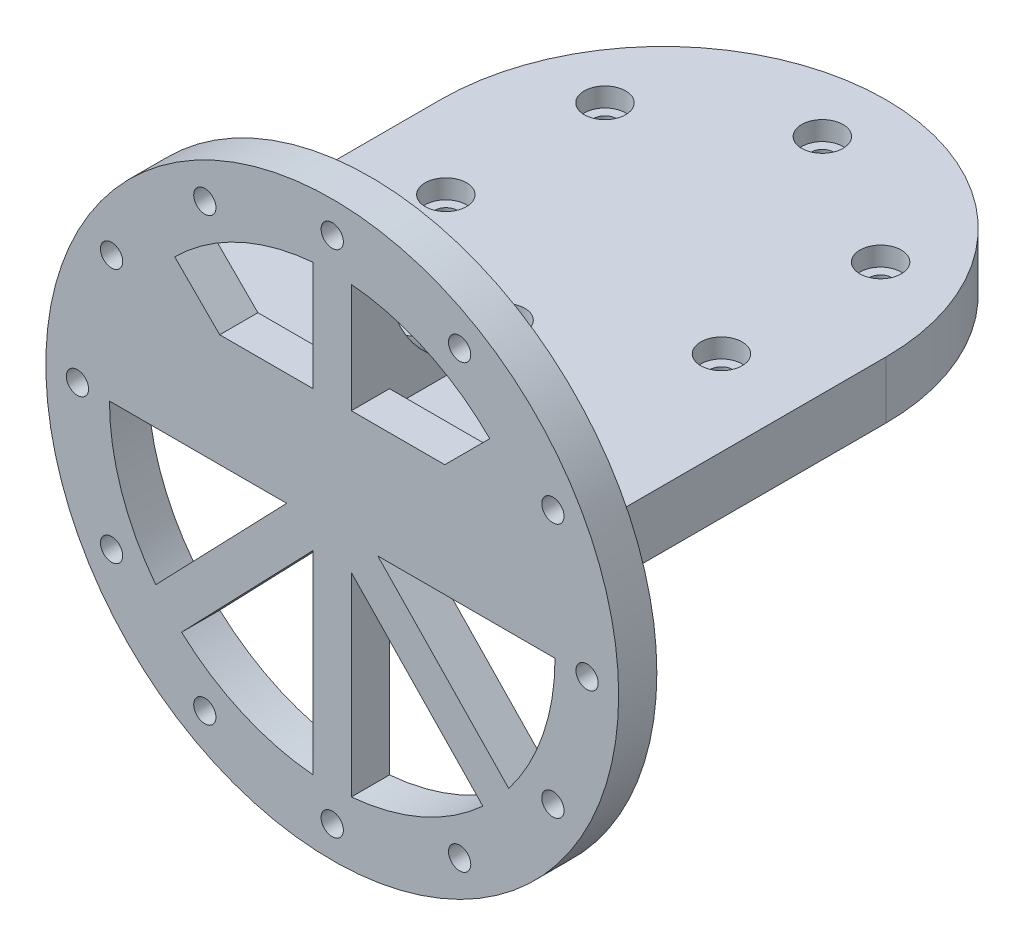
SolidWorks part; units mm, degrees
ref_plane "Front Plane" through (0, 0, 0) normal (0, 0, 1) x (1, 0, 0)
ref_plane "Top Plane" through (0, 0, 0) normal (0, 1, 0) x (1, 0, 0)
ref_plane "Right Plane" through (0, 0, 0) normal (1, 0, 0) x (0, 0, -1)
sketch "Sketch1" plane through (0, 0, 0) normal (0, 1, 0) x (1, 0, 0)
  circle A0 centre (0, 0) radius 35
  dimension "D1" = 70
extrude "Boss-Extrude1" add sketch "Sketch1" along normal blind 9
sketch "Sketch2" plane through (0, 0, 0) normal (0, -1, 0) x (1, 0, 0)
  circle A0 centre (0, 0) radius 30
  dimension "D1" = 60
extrude "Cut-Extrude1" cut sketch "Sketch2" against normal blind 3
sketch "Sketch3" plane through (0, 9, 0) normal (0, 1, 0) x (1, 0, 0)
  line L0 (0, 0) -> (0, -25) construction
  circle A0 centre (0, 0) radius 25 construction
  circle A1 centre (0, -25) radius 1.75
  circle A2 centre (-21.6506, -12.5) radius 1.75
  circle A3 centre (-21.6506, 12.5) radius 1.75
  circle A4 centre (0, 25) radius 1.75
  circle A5 centre (21.6506, 12.5) radius 1.75
  circle A6 centre (21.6506, -12.5) radius 1.75
  point P17 (0, 0)
  dimension "D1" = 50
  dimension "D2" = 3.5
  dimension "D3" = 6
extrude "Cut-Extrude2" cut sketch "Sketch3" against normal through all
sketch "Sketch4" plane through (0, 9, 0) normal (0, 1, 0) x (1, 0, 0)
  circle A0 centre (0, 25) radius 3.25
  circle A1 centre (21.6506, 12.5) radius 3.25
  circle A2 centre (21.6506, -12.5) radius 3.25
  circle A3 centre (0, -25) radius 3.25
  circle A4 centre (-21.6506, -12.5) radius 3.25
  circle A5 centre (-21.6506, 12.5) radius 3.25
  point P15 (0, 0)
  dimension "D1" = 6.5
  dimension "D2" = 6
extrude "Cut-Extrude3" cut sketch "Sketch4" against normal blind 3
sketch "Sketch5" plane through (0, 9, 0) normal (0, 1, 0) x (1, 0, 0)
  line L0 (-35, 0) -> (35, 0) construction
  line L1 (0, 0) -> (0, -35) construction
  line L2 (-35, 0) -> (-35, -52)
  line L3 (-35, -52) -> (35, -52)
  line L4 (35, -52) -> (35, 0)
  circle A0 centre (0, 0) radius 35 construction
  arc A1 (-35, 0) -> (35, 0) centre (0, 0) ccw
  circle M14 centre (0, 0) radius 35
  dimension "D1" = 52
extrude "Boss-Extrude3" add sketch "Sketch5" against normal blind 9 contours M14 region at (0, 9, 38.4996)
sketch "Sketch21" plane through (0, 0, 0) normal (0, -1, 0) x (1, 0, 0)
  line L0 (-35, 0) -> (-35, 52) construction
  line L1 (35, 52) -> (-35, 52)
  line L2 (35, 52) -> (35, 46)
  line L3 (35, 46) -> (-35, 46)
  line L4 (-35, 52) -> (-35, 46)
  dimension "D1" = 6
extrude "Boss-Extrude8" add sketch "Sketch21" along normal blind 6
sketch "Sketch26" plane through (0, 0, 52) normal (0, 0, 1) x (1, 0, 0)
  line L0 (35, -6) -> (-35, -6) construction
  circle A0 centre (0, -6) radius 45
  dimension "D1" = 90
extrude "Boss-Extrude12" add sketch "Sketch26" against normal blind 6
sketch "Sketch27" plane through (0, 0, 52) normal (0, 0, 1) x (1, 0, 0)
  line L0 (0, -51) -> (0, 39) construction
  line L1 (45, -6) -> (-45, -6) construction
  circle A0 centre (0, -6) radius 45 construction
  circle A1 centre (0, -6) radius 40 construction
  circle A2 centre (0, -46.0317) radius 1.75
  circle A3 centre (-20.0158, -40.6685) radius 1.75
  circle A4 centre (-34.6685, -26.0158) radius 1.75
  circle A5 centre (-40.0317, -6) radius 1.75
  circle A6 centre (-34.6685, 14.0158) radius 1.75
  circle A7 centre (-20.0158, 28.6685) radius 1.75
  circle A8 centre (0, 34.0317) radius 1.75
  circle A9 centre (20.0158, 28.6685) radius 1.75
  circle A10 centre (34.6685, 14.0158) radius 1.75
  circle A11 centre (40.0317, -6) radius 1.75
  circle A12 centre (34.6685, -26.0158) radius 1.75
  circle A13 centre (20.0158, -40.6685) radius 1.75
  point P35 (0, -6)
  dimension "D1" = 80
  dimension "D2" = 3.5
  dimension "D3" = 12
extrude "Cut-Extrude20" cut sketch "Sketch27" against normal up to next
sketch "Sketch28" plane through (0, 0, 46) normal (0, 0, -1) x (-1, 0, 0)
  line L0 (45, -6) -> (0, -6) construction
  circle A1 centre (0, -46.0317) radius 3.25
  circle A2 centre (0, -6) radius 45 construction
  circle A3 centre (-20, -40.6727) radius 3.25
  circle A4 centre (-34.641, -26.0317) radius 3.25
  circle A5 centre (-40, -6.0317) radius 3.25
  circle A6 centre (-34.641, 13.9683) radius 3.25
  circle A7 centre (-20, 28.6093) radius 3.25
  circle A8 centre (0, 33.9683) radius 3.25
  circle A9 centre (20, 28.6093) radius 3.25
  circle A10 centre (34.641, 13.9683) radius 3.25
  circle A11 centre (40, -6.0317) radius 3.25
  circle A12 centre (34.641, -26.0317) radius 3.25
  circle A13 centre (20, -40.6727) radius 3.25
  point P32 (0, -6.0317)
  dimension "D1" = 6.5
extrude "Cut-Extrude21" cut sketch "Sketch28" against normal blind 3
sketch "Sketch30" plane through (0, 0, 46) normal (0, 0, -1) x (-1, 0, 0)
  line L0 (-45, -6) -> (45, -6) construction
  line L1 (0, -51) -> (0, -6) construction
  line L2 (-3, -10.325) -> (-3, -40.8712)
  line L3 (3, -10.325) -> (3, -40.8712)
  line L4 (-7.1648, -6) -> (-35, -6)
  line L5 (7.1648, -6) -> (35, -6)
  line L6 (0, -6) -> (-31.8198, 25.8198) construction
  line L7 (0, -6) -> (31.8198, 25.8198) construction
  line L8 (-24.7487, 18.7487) -> (-17.6777, 11.6777)
  line L9 (17.6777, 11.6777) -> (24.7487, 18.7487)
  line L10 (-17.6777, 11.6777) -> (-3, 11.6777)
  line L11 (-3, -6) -> (-25.7876, -29.6643) construction
  line L12 (-3, -10.325) -> (-23.666, -31.7861)
  line L13 (-7.1648, -6) -> (-27.7295, -27.3559)
  line L14 (7.1648, -6) -> (27.7295, -27.3559)
  line L15 (3, -10.325) -> (23.666, -31.7861)
  line L16 (3, 11.6777) -> (17.6777, 11.6777)
  line L17 (3, 11.6777) -> (3, 28.8712)
  line L18 (-3, 11.6777) -> (-3, 28.8712)
  circle A0 centre (0, -6) radius 45 construction
  arc A1 (-35, -6) -> (-27.7295, -27.3559) centre (0, -6) ccw
  arc A2 (3, -40.8712) -> (23.666, -31.7861) centre (0, -6) ccw
  arc A3 (-24.7487, 18.7487) -> (-3, 28.8712) centre (0, -6) cw
  arc A4 (27.7295, -27.3559) -> (35, -6) centre (0, -6) ccw
  arc A5 (-23.666, -31.7861) -> (-3, -40.8712) centre (0, -6) ccw
  arc A6 (3, 28.8712) -> (24.7487, 18.7487) centre (0, -6) cw
  dimension "D1" = 70
  dimension "D4" = 35
  dimension "D5" = 3
  dimension "D2" = 3
  dimension "D3" = 135
  dimension "D6" = 3
extrude "Cut-Extrude23" cut sketch "Sketch30" against normal through all
sketch "Sketch32" plane through (0, 0, 0) normal (1, 0, 0) x (0, 0, -1)
  line L0 (-31, 9) -> (-46, 9)
  line L1 (0, 9) -> (-46, 9) construction
  line L2 (-46, 9) -> (-46, 24)
  line L4 (-31, 9) -> (-43, 12) construction
  line L5 (-43, 12) -> (-46, 24) construction
  spline S0 degree 2 poles (-31, 9) (-43, 12) (-46, 24) knots 0 0 0 1 1 1
  dimension "D1" = 15
  dimension "D2" = 15
  dimension "D3" = 3
  dimension "D4" = 3
extrude "Boss-Extrude13" add sketch "Sketch32" along normal blind 3 and the other way blind 3
